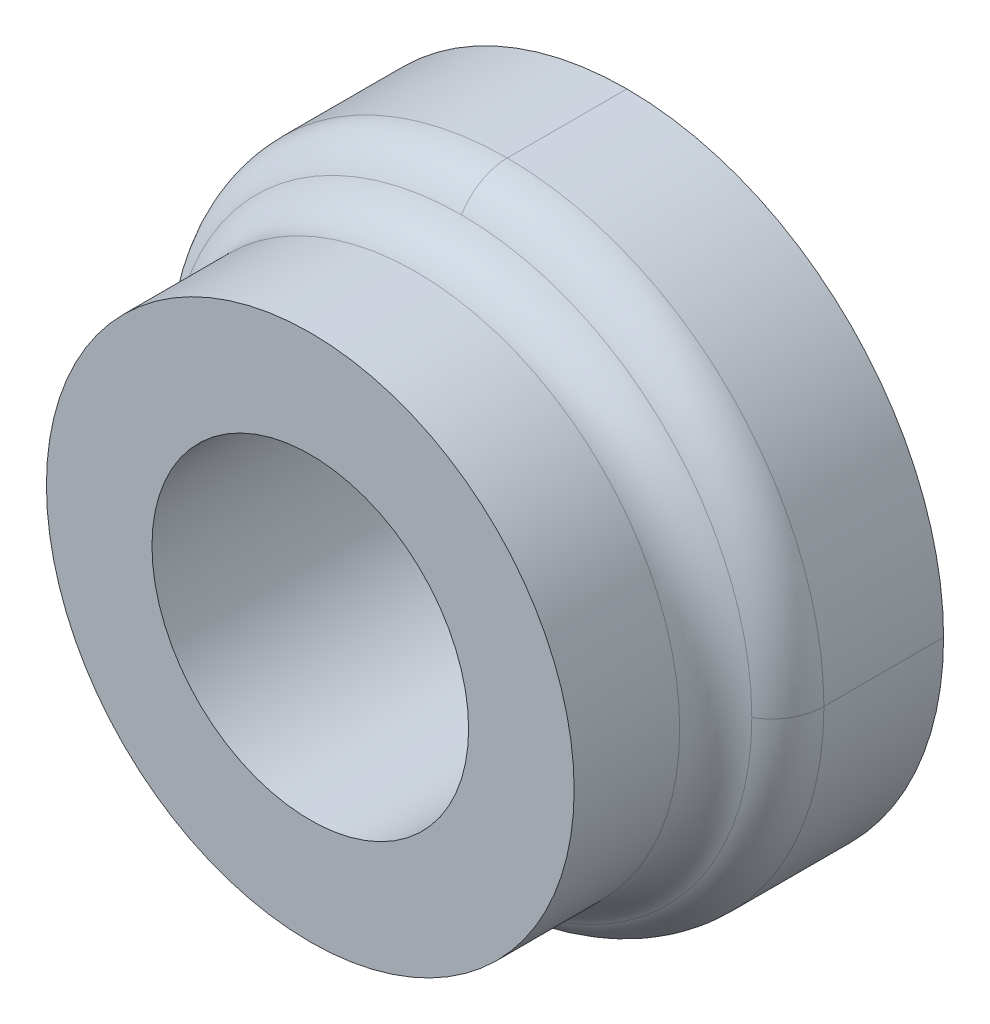
SolidWorks part; units mm, degrees
ref_plane "Alzado" through (0, 0, 0) normal (0, 0, 1) x (1, 0, 0)
ref_plane "Planta" through (0, 0, 0) normal (0, 1, 0) x (1, 0, 0)
ref_plane "Vista lateral" through (0, 0, 0) normal (1, 0, 0) x (0, 0, -1)
sketch "Croquis1" plane through (0, 0, 0) normal (0, 0, 1) x (1, 0, 0)
sketch "Croquis4" plane through (0, 0, 0) normal (0, 0, 1) x (1, 0, 0)
  line L1 (-3, -3) -> (3, -3)
  line L2 (-3, -3) -> (-3, 3)
  line L3 (-3, 3) -> (3, 3)
  line L4 (3, -3) -> (3, 3)
  line L5 (-3, -3) -> (3, 3) construction
  line L6 (-3, 3) -> (3, -3) construction
  circle A0 centre (0, 0) radius 2.5
  circle A1 centre (0, 0) radius 1.5
  dimension "D1" = 5
  dimension "D2" = 3
  dimension "D3" = 6
  dimension "D4" = 6
extrude "Saliente-Extruir3" add sketch "Croquis4" along normal blind 3 contours A0 A1 region at (-2.4293, 0, 0)
extrude "Saliente-Extruir4" add sketch "Croquis4<4>" along normal blind 1.5 contours L1 L4 L3 L2 A0 region at (-2.9151, 0, 0)
sketch "Croquis4<4>" plane through (0, 0, 0) normal (0, 0, 1) x (1, 0, 0) same geometry as "Croquis4"
fillet "Redondeo6" radius 3 4 edges at (-3, 3, 0.75) (3, 3, 0.75) (3, -3, 0.75) (-3, -3, 0.75)
fillet "Redondeo8" radius 0.5 1 edges at (2.5, 0, 1.5)
fillet "Redondeo9" radius 0.5 4 edges at (-2.1213, -2.1213, 1.5) (-2.1213, 2.1213, 1.5) (2.1213, 2.1213, 1.5) (2.1213, -2.1213, 1.5)
fillet "Redondeo10" radius 0.5 1 edges at (1.5, 0, 0)
